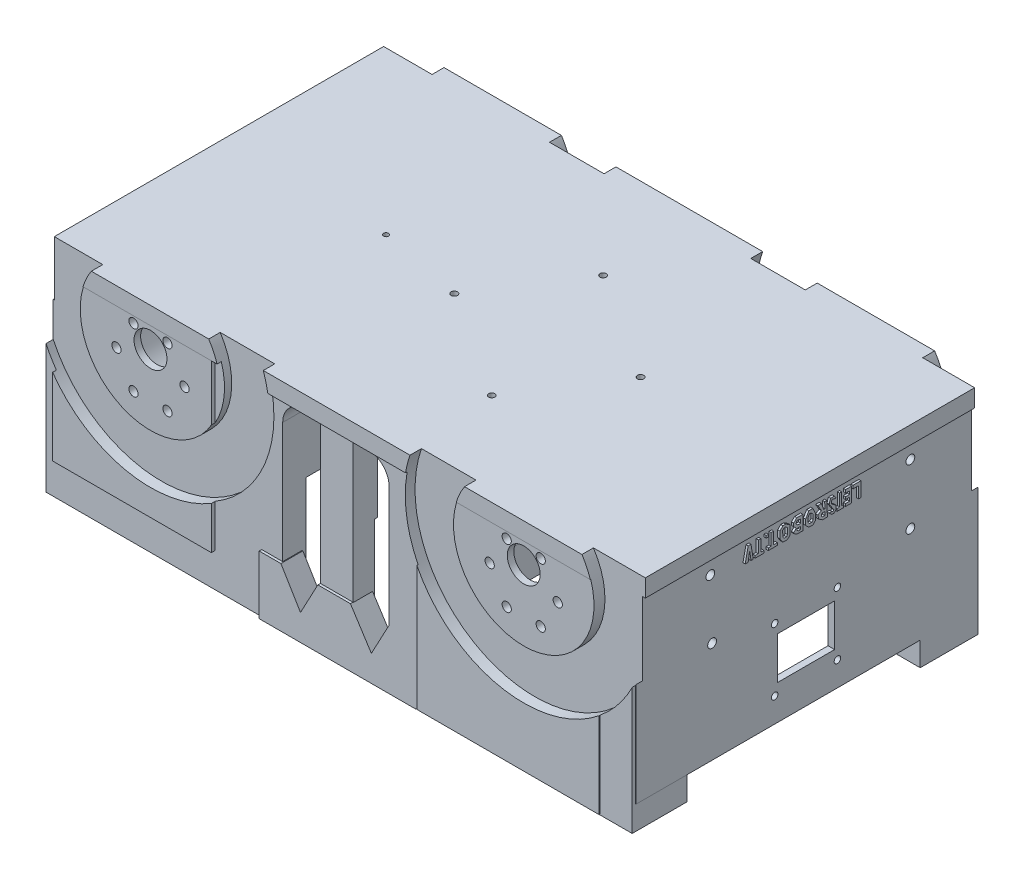
SolidWorks part; units mm, degrees
ref_plane "Front Plane" through (0, 0, 0) normal (0, 0, 1) x (1, 0, 0)
ref_plane "Top Plane" through (0, 0, 0) normal (0, 1, 0) x (1, 0, 0)
ref_plane "Right Plane" through (0, 0, 0) normal (1, 0, 0) x (0, 0, -1)
sketch "MotorHoldersSketch" plane through (0, 0, 0) normal (0, 0, 1) x (1, 0, 0)
  line L0 (0, 0) -> (170, 0) construction
  line L1 (0, 0) -> (0, 23.41) construction
  line L2 (170, 0) -> (170, 23.41) construction
  circle A0 centre (0, 0) radius 23.41
  circle A1 centre (170, 0) radius 23.41
ref_axis "MotorCenterAxis1" through (0, 0, 0) along (0, 0, 1)
ref_axis "MotorCenterAxis2" through (170, 0, 0) along (0, 0, 1)
extrude "MotorHolders" add sketch "MotorHoldersSketch" along normal blind 80 and the other way blind 80
sketch "Sketch3" plane through (0, 0, 0) normal (0, 0, 1) x (1, 0, 0)
  line L1 (1.9406, 21.133) -> (168.3435, 21.133)
  line L2 (1.9406, 21.133) -> (1.9406, 18.3155)
  line L3 (1.9406, 18.3155) -> (168.3435, 18.3155)
  line L4 (168.3435, 21.133) -> (168.3435, 18.3155)
sketch "Sketch4" plane through (0, 0, 0) normal (0, 1, 0) x (1, 0, 0)
  line L1 (221.2811, -76.3794) -> (-41.4939, -76.3794)
  line L2 (221.2811, -76.3794) -> (221.2811, 76.7331)
  line L3 (221.2811, 76.7331) -> (-41.4939, 76.7331)
  line L4 (-41.4939, -76.3794) -> (-41.4939, 76.7331)
extrude "Cut-Extrude1" cut sketch "Sketch4" against normal blind 26
ref_axis "Axis3" through (170, 0, 0) along (0, -1, 0)
sketch3d "ReferencePlanePosition"
  line L0 (170, 0, 0) -> (170, -34.8293, 0)
  line L1 (170, 0, 0) -> (170, -38.994, 0) construction
ref_plane "ReferencePlane" through (170, -34.8293, 0) normal (0, -1, 0) x (-1, 0, 0)
sketch "Sketch6" plane through (170, -34.8293, 0) normal (0, -1, 0) x (-1, 0, 0)
  line L1 (219.5858, 78.949) -> (112.1002, 78.949)
  line L2 (219.5858, 78.949) -> (219.5858, 65.5282)
  line L3 (219.5858, 65.5282) -> (112.1002, 65.5282)
  line L4 (112.1002, 78.949) -> (112.1002, 65.5282)
  line L5 (219.3147, -40.0209) -> (111.499, -40.0209)
  line L6 (219.3147, -40.0209) -> (219.3147, -78.2822)
  line L7 (219.3147, -78.2822) -> (111.499, -78.2822)
  line L8 (111.499, -40.0209) -> (111.499, -78.2822)
  line L9 (61.4891, 77.8627) -> (19.9904, 77.8627)
  line L10 (61.4891, 77.8627) -> (61.4891, 40.7512)
  line L11 (61.4891, 40.7512) -> (19.9904, 40.7512)
  line L12 (19.9904, 77.8627) -> (19.9904, 40.7512)
  line L13 (61.8484, -44.1716) -> (20.0852, -44.1716)
  line L14 (61.8484, -44.1716) -> (61.8484, -79.4437)
  line L15 (61.8484, -79.4437) -> (20.0852, -79.4437)
  line L16 (20.0852, -44.1716) -> (20.0852, -79.4437)
  line L17 (213.765, 73.0364) -> (192.9548, 73.0364)
  line L18 (213.765, 73.0364) -> (213.765, 71.0153)
  line L19 (213.765, 71.0153) -> (192.9548, 71.0153)
  line L20 (192.9548, 73.0364) -> (192.9548, 71.0153)
  line L21 (41.3552, 69.1777) -> (28.5109, 69.1777)
  line L22 (41.3552, 69.1777) -> (41.3552, 50.8413)
  line L23 (41.3552, 50.8413) -> (28.5109, 50.8413)
  line L24 (28.5109, 69.1777) -> (28.5109, 50.8413)
  line L25 (43.3068, -72.8101) -> (32.1723, -72.8101)
  line L26 (43.3068, -72.8101) -> (43.3068, -54.7747)
  line L27 (43.3068, -54.7747) -> (32.1723, -54.7747)
  line L28 (32.1723, -72.8101) -> (32.1723, -54.7747)
  line L29 (211.9411, -70.4881) -> (201.0982, -70.4881)
  line L30 (211.9411, -70.4881) -> (211.9411, -60.1404)
  line L31 (211.9411, -60.1404) -> (201.0982, -60.1404)
  line L32 (201.0982, -70.4881) -> (201.0982, -60.1404)
  line L33 (97.1795, 78.949) -> (79.4162, 78.949)
  line L34 (97.1795, 78.949) -> (97.1795, 67.7632)
  line L35 (97.1795, 67.7632) -> (79.4162, 67.7632)
  line L36 (79.4162, 78.949) -> (79.4162, 67.7632)
  line L37 (58.6711, 51.3198) -> (53.8697, 51.3198)
  line L38 (58.6711, 51.3198) -> (58.6711, 67.7632)
  line L39 (58.6711, 67.7632) -> (53.8697, 67.7632)
  line L40 (53.8697, 51.3198) -> (53.8697, 67.7632)
  line L41 (94.2281, -78.2822) -> (79.4162, -78.2822)
  line L42 (94.2281, -78.2822) -> (94.2281, -67.2515)
  line L43 (94.2281, -67.2515) -> (79.4162, -67.2515)
  line L44 (79.4162, -78.2822) -> (79.4162, -67.2515)
  line L45 (56.3648, -69.8638) -> (51.7107, -69.8638)
  line L46 (56.3648, -69.8638) -> (56.3648, -55.4273)
  line L47 (56.3648, -55.4273) -> (51.7107, -55.4273)
  line L48 (51.7107, -69.8638) -> (51.7107, -55.4273)
  line L49 (-20.7001, -79.4437) -> (-48.8506, -79.4437)
  line L50 (-20.7001, -79.4437) -> (-20.7001, -54.5097)
  line L51 (-20.7001, -54.5097) -> (-48.8506, -54.5097)
  line L52 (-48.8506, -79.4437) -> (-48.8506, -54.5097)
  line L53 (-18.3873, 77.8627) -> (-49.0581, 77.8627)
  line L54 (-18.3873, 77.8627) -> (-18.3873, 51.5325)
  line L55 (-18.3873, 51.5325) -> (-49.0581, 51.5325)
  line L56 (-49.0581, 77.8627) -> (-49.0581, 51.5325)
  line L57 (-41.8141, -72.8101) -> (-31.6362, -72.8101)
  line L58 (-41.8141, -72.8101) -> (-41.8141, -62.9794)
  line L59 (-41.8141, -62.9794) -> (-31.6362, -62.9794)
  line L60 (-31.6362, -72.8101) -> (-31.6362, -62.9794)
  line L61 (-31.6362, 69.1777) -> (-41.5347, 69.1777)
  line L62 (-31.6362, 69.1777) -> (-31.6362, 58.5421)
  line L63 (-31.6362, 58.5421) -> (-41.5347, 58.5421)
  line L64 (-41.5347, 69.1777) -> (-41.5347, 58.5421)
extrude "PowerBankHolders" add sketch "Sketch6" along normal blind 40 and the other way blind 59 separate body
sketch3d "3DSketch3"
  line L0 (170, 0, 0) -> (170, -64.5, 0) construction
ref_plane "Plane2" through (170, -64.5, 0) normal (0, -1, 0) x (-1, 0, 0)
sketch "Sketch7" plane through (170, -64.5, 0) normal (0, -1, 0) x (-1, 0, 0)
  line L1 (-9.5047, -80.801) -> (181.32, -80.801)
  line L2 (-9.5047, -80.801) -> (-9.5047, 73.8662)
  line L3 (-9.5047, 73.8662) -> (181.32, 73.8662)
  line L4 (181.32, -80.801) -> (181.32, 73.8662)
  line L5 (151.8712, -54.3972) -> (26.5361, -54.3972)
  line L6 (151.8712, -54.3972) -> (151.8712, 46.2413)
  line L7 (151.8712, 46.2413) -> (26.5361, 46.2413)
  line L8 (26.5361, -54.3972) -> (26.5361, 46.2413)
ref_point "Point1"
ref_point "Point2"
sketch3d "3DSketch11"
  line L0 (0, 0, -80) -> (170, 0, 80) construction
  point P4 (85, 0, 0)
sketch "MotorHolderExtrudeSketch" plane through (0, 0, 0) normal (0, 0, 1) x (1, 0, 0)
  circle A0 centre (170, 0) radius 20.415
  circle A1 centre (0, 0) radius 20.415
  circle A3 centre (0, 0) radius 23.41 construction
  circle A4 centre (170, 0) radius 23.41 construction
ref_point "TopOfMotors"
ref_plane "TangentToTopOfMotors" through (0, -20.415, 0) normal (0, 1, 0) x (1, 0, 0)
ref_axis "Axis4" through (85, 0, 0) along (0, -1, 0)
ref_plane "BottomOfPowerBankRegion" through (0, -20.425, 0) normal (0, 1, 0) x (1, 0, 0)
ref_point "CenterAtBottomOfPowerBank"
ref_plane "TopOfPowerBankPlane" through (0, -54.425, 0) normal (0, 1, 0) x (1, 0, 0)
sketch "Sketch13" plane through (0, -54.425, 0) normal (0, 1, 0) x (1, 0, 0)
  line L1 (-19.4498, 72.5454) -> (166.1636, 72.5454)
  line L2 (-19.4498, 72.5454) -> (-19.4498, -78.2051)
  line L3 (-19.4498, -78.2051) -> (166.1636, -78.2051)
  line L4 (166.1636, 72.5454) -> (166.1636, -78.2051)
  line L5 (19.3173, -49.583) -> (137.9607, -49.583)
  line L6 (19.3173, -49.583) -> (19.3173, -21.0549)
  line L7 (19.3173, -21.0549) -> (137.9607, -21.0549)
  line L8 (137.9607, -49.583) -> (137.9607, -21.0549)
  line L9 (19.3173, 56.6778) -> (137.9607, 56.6778)
  line L10 (19.3173, 56.6778) -> (19.3173, 36.3234)
  line L11 (19.3173, 36.3234) -> (137.9607, 36.3234)
  line L12 (137.9607, 56.6778) -> (137.9607, 36.3234)
  line L13 (19.3173, 18.3186) -> (137.9607, 18.3186)
  line L14 (19.3173, 18.3186) -> (19.3173, -7.3615)
  line L15 (19.3173, -7.3615) -> (137.9607, -7.3615)
  line L16 (137.9607, 18.3186) -> (137.9607, -7.3615)
sketch "Sketch15" plane through (150.0096, 0, 0) normal (1, 0, 0) x (0, 0, -1)
  line L1 (72.5313, -25.7765) -> (45.7099, -25.7765)
  line L2 (72.5313, -25.7765) -> (72.5313, -24.2242)
  line L3 (72.5313, -24.2242) -> (45.7099, -24.2242)
  line L4 (45.7099, -25.7765) -> (45.7099, -24.2242)
ref_plane "Plane6" through (0, 0, 0) normal (0, 0, 1) x (1, 0, 0)
sketch "MotorGeometry1" plane through (0, 0, 0) normal (0, 0, 1) x (1, 0, 0)
  line L0 (170, 0) -> (170, -13.42)
  line L1 (170, 0) -> (170, -34.8293) construction
  line L2 (170, -13.42) -> (162.25, -13.42) construction
  line L3 (170, -13.42) -> (177.75, -13.42) construction
  line L4 (170, -13.42) -> (170, 7) construction
  line L5 (170, 0) -> (185.5, 0) construction
  line L6 (170, 0) -> (154.5, 0) construction
  line L7 (170, 0) -> (170, 13.42) construction
  line L8 (170, 0) -> (170, 23.41) construction
  line L9 (170, 13.42) -> (177.75, 13.42) construction
  line L10 (170, 13.42) -> (162.25, 13.42)
ref_axis "BoltAxisA" through (185.5, 0, 0) along (0, 0, 1)
ref_axis "BoltAxisB" through (177.75, -13.42, 0) along (0, 0, 1)
ref_axis "BoltAxisC" through (162.25, -13.42, 0) along (0, 0, 1)
ref_axis "BoltAxisD" through (154.5, 0, 0) along (0, 0, 1)
ref_axis "BoltAxisE" through (162.25, 13.42, 0) along (0, 0, 1)
ref_axis "BoltAxisF" through (177.75, 13.42, 0) along (0, 0, 1)
ref_point "Point6"
ref_point "Point7"
ref_point "Point8"
ref_point "Point9"
ref_point "Point10"
ref_point "Point11"
ref_point "Point12"
ref_point "Point13"
ref_point "Point14"
ref_point "Point15"
ref_point "Point16"
ref_point "Point17"
ref_plane "Plane7" through (0, 0, 0) normal (0, 0, 1) x (1, 0, 0)
sketch "MotorGeometry2" plane through (0, 0, 0) normal (0, 0, 1) x (1, 0, 0)
  line L0 (0, 0) -> (0, -13.42) construction
  line L1 (0, -13.42) -> (7.75, -13.42) construction
  line L2 (0, -13.42) -> (-7.75, -13.42) construction
  line L3 (0, 0) -> (0, 13.42)
  line L4 (0, -13.42) -> (0, 7) construction
  line L5 (0, 13.42) -> (7.75, 13.42) construction
  line L6 (0, 13.42) -> (-7.75, 13.42) construction
  line L7 (0, 0) -> (15.5, 0) construction
  line L8 (0, 0) -> (-15.5, 0) construction
  line L9 (0, 0) -> (0, 23.41) construction
ref_axis "Axis11" through (15.5, 0, 0) along (0, 0, 1)
ref_axis "Axis12" through (7.75, 13.42, 0) along (0, 0, 1)
ref_axis "Axis13" through (-7.75, 13.42, 0) along (0, 0, 1)
ref_axis "Axis14" through (-15.5, 0, 0) along (0, 0, 1)
ref_axis "Axis15" through (-7.75, -13.42, 0) along (0, 0, 1)
ref_axis "Axis16" through (7.75, -13.42, 0) along (0, 0, 1)
ref_point "Point18"
ref_point "Point19"
ref_point "Point20"
ref_point "Point21"
ref_point "Point22"
ref_point "Point23"
ref_point "Point24"
ref_point "Point25"
ref_point "Point26"
ref_point "Point27"
ref_point "Point28"
ref_point "Point29"
ref_plane "BottomPlane" through (0, 19.575, 0) normal (0, 1, 0) x (1, 0, 0)
ref_axis "OutputShaftReference1" through (0, 7, 0) along (0, 0, 1)
ref_point "Point35"
ref_axis "OutputShaftReference2" through (170, 7, 0) along (0, 0, 1)
sketch "Sketch21" plane through (0, 19.575, 0) normal (0, 1, 0) x (1, 0, 0)
  line L0 (219.6842, -79.5488) -> (-50.341, -79.5488) construction
  line L1 (-50.341, -79.5488) -> (-50.341, 79.7899) construction
  line L2 (-50.341, 79.7899) -> (219.6842, 79.7899) construction
  line L3 (219.6842, 79.7899) -> (219.6842, -79.5488) construction
  circle A0 centre (85, 0) radius 156.3953
extrude "BottomPlate" add sketch "Sketch21" along normal blind 5 and the other way blind 3
ref_plane "HoleReferencePlane1" through (0, 0, 80) normal (0, 0, 1) x (1, 0, 0)
ref_point "OutputShaftPosition3"
ref_point "OutputShaftPosition1"
sketch "Sketch23" plane through (0, 0, 80) normal (0, 0, 1) x (1, 0, 0)
  line L1 (27.7411, -59.3229) -> (-44.5901, -59.3229)
  line L2 (27.7411, -59.3229) -> (27.7411, 21.8402)
  line L3 (27.7411, 21.8402) -> (-44.5901, 21.8402)
  line L4 (-44.5901, -59.3229) -> (-44.5901, 21.8402)
  line L5 (121.3218, 21.8402) -> (204.258, 21.8402)
  line L6 (121.3218, 21.8402) -> (121.3218, -74.371)
  line L7 (121.3218, -74.371) -> (204.258, -74.371)
  line L8 (204.258, 21.8402) -> (204.258, -74.371)
extrude "MotorMountingSupport1" add sketch "Sketch23" against normal blind 6
ref_plane "HoleReferencePlane2" through (0, 0, -80) normal (0, 0, -1) x (-1, 0, 0)
ref_point "OutputShaftPosition4"
ref_point "OutputShaftPosition2"
sketch "Sketch24" plane through (0, 0, -80) normal (0, 0, -1) x (-1, 0, 0)
  line L1 (-202.1905, -75.2023) -> (-123.8485, -75.2023)
  line L2 (-202.1905, -75.2023) -> (-202.1905, 19.2374)
  line L3 (-202.1905, 19.2374) -> (-123.8485, 19.2374)
  line L4 (-123.8485, -75.2023) -> (-123.8485, 19.2374)
  line L5 (-24.3642, -64.1521) -> (29.5505, -64.1521)
  line L6 (-24.3642, -64.1521) -> (-24.3642, 22.5226)
  line L7 (-24.3642, 22.5226) -> (29.5505, 22.5226)
  line L8 (29.5505, -64.1521) -> (29.5505, 22.5226)
extrude "MotorMountingSuppor2" add sketch "Sketch24" against normal blind 6
sketch "Sketch17" plane through (0, 0, 80) normal (0, 0, 1) x (1, 0, 0)
  circle A0 centre (185.5, 0) radius 2.1
  circle A1 centre (177.75, -13.42) radius 2.1
  circle A2 centre (162.25, -13.42) radius 2.1
  circle A3 centre (154.5, 0) radius 2.1
  circle A4 centre (162.25, 13.42) radius 2.1
  circle A5 centre (177.75, 13.42) radius 2.1
  circle A6 centre (170, 7) radius 7.5
extrude "MotorHoles1" cut sketch "Sketch17" against normal blind 31.5
sketch "Sketch19" plane through (0, 0, -80) normal (0, 0, -1) x (-1, 0, 0)
  circle A0 centre (-185.5, 0) radius 2.1
  circle A1 centre (-177.75, -13.42) radius 2.1
  circle A2 centre (-162.25, -13.42) radius 2.1
  circle A3 centre (-154.5, 0) radius 2.1
  circle A4 centre (-162.25, 13.42) radius 2.1
  circle A5 centre (-177.75, 13.42) radius 2.1
  circle A6 centre (-170, 7) radius 7.5
sketch "BoltHolesSketch3" plane through (0, 0, 80) normal (0, 0, 1) x (1, 0, 0)
  circle A0 centre (7.75, -13.42) radius 2.1
  circle A1 centre (15.5, 0) radius 2.1
  circle A2 centre (7.75, 13.42) radius 2.1
  circle A3 centre (-7.75, 13.42) radius 2.1
  circle A4 centre (-15.5, 0) radius 2.1
  circle A5 centre (-7.75, -13.42) radius 2.1
  circle A6 centre (0, 7) radius 7.5
extrude "Cut-Extrude4" cut sketch "Sketch19" against normal blind 30
extrude "MotorHoles3" cut sketch "BoltHolesSketch3" against normal blind 31.5
sketch "BoltHolesSketch4" plane through (0, 0, -80) normal (0, 0, -1) x (-1, 0, 0)
  circle A0 centre (-15.5, 0) radius 2.1
  circle A1 centre (-7.75, 13.42) radius 2.1
  circle A2 centre (7.75, 13.42) radius 2.1
  circle A3 centre (15.5, 0) radius 2.1
  circle A4 centre (7.75, -13.42) radius 2.1
  circle A5 centre (-7.75, -13.42) radius 2.1
  circle A6 centre (0, 7) radius 7.5
extrude "MotorHoles4" cut sketch "BoltHolesSketch4" against normal blind 15
ref_plane "Front" through (219.0581, 0, 0) normal (1, 0, 0) x (0, 0, -1)
sketch "Sketch29" plane through (219.0581, 0, 0) normal (1, 0, 0) x (0, 0, -1)
  line L1 (76.6955, -63.9254) -> (-77.9397, -63.9254)
  line L2 (76.6955, -63.9254) -> (76.6955, 20.2062)
  line L3 (76.6955, 20.2062) -> (-77.9397, 20.2062)
  line L4 (-77.9397, -63.9254) -> (-77.9397, 20.2062)
  line L5 (-13.4507, -48.1531) -> (12.5493, -48.1531)
  line L6 (-13.4507, -48.1531) -> (-13.4507, -28.9404)
  line L7 (-13.4507, -28.9404) -> (12.5493, -28.9404)
  line L8 (12.5493, -48.1531) -> (12.5493, -28.9404)
extrude "Boss-Extrude8" add sketch "Sketch29" against normal blind 3
ref_plane "RaspberryPiBasePlane" through (0, 16.575, 0) normal (0, -1, 0) x (-1, 0, 0)
sketch "Sketch27" plane through (0, 16.575, 0) normal (0, -1, 0) x (-1, 0, 0)
  line L1 (31.6337, 64.5517) -> (-194.8264, 64.5517)
  line L2 (31.6337, 64.5517) -> (31.6337, -65.4335)
  line L3 (31.6337, -65.4335) -> (-194.8264, -65.4335)
  line L4 (-194.8264, 64.5517) -> (-194.8264, -65.4335)
extrude "Boss-Extrude6" add sketch "Sketch27" against normal blind 3
ref_plane "Plane12" through (0, -74.8293, 0) normal (0, -1, 0) x (-1, 0, 0)
sketch "Sketch28" plane through (0, -74.8293, 0) normal (0, -1, 0) x (-1, 0, 0)
  line L1 (-189.3897, -97.3973) -> (-123.0026, -97.3973)
  line L2 (-189.3897, -97.3973) -> (-189.3897, 96.7192)
  line L3 (-189.3897, 96.7192) -> (-123.0026, 96.7192)
  line L4 (-123.0026, -97.3973) -> (-123.0026, 96.7192)
sketch "Sketch40" plane through (0, 16.575, 0) normal (0, -1, 0) x (1, 0, 0)
  line L1 (-49.5858, -65.5282) -> (-15.7443, -65.5282)
  line L2 (-49.5858, -65.5282) -> (-49.5858, -33.9964)
  line L3 (-49.5858, -33.9964) -> (-15.7443, -33.9964)
  line L4 (-15.7443, -65.5282) -> (-15.7443, -33.9964)
extrude "Boss-Extrude11" add sketch "Sketch40" along normal blind 40
fillet "Fillet2" radius 15 1 edges at (-33.0588, 16.575, -33.9964) type face fillet first side face at (-28.7089, -2.1691, -33.9964) second side face at (85, 16.575, 156.3953)
fillet "Fillet3" radius 15 1 edges at (-32.6651, -23.425, -65.5282) type face fillet first side face at (-5.65, -13.42, -65.5282) second side face at (-32.6651, -23.425, -49.7623)
sketch "Sketch11" plane through (0, -20.425, 0) normal (0, 1, 0) x (1, 0, 0)
  line L0 (-34.2162, 4.2922) -> (204.2162, -4.2922) construction
  line L5 (-34.2162, -64.7581) -> (-34.2162, 73.3425)
  line L6 (204.2162, 63.611) -> (204.2162, -72.1954)
  line L7 (204.2162, -72.1954) -> (-34.2162, -64.7581)
  line L8 (204.2162, 63.611) -> (-34.2162, 73.3425)
  circle A0 centre (85, 0) radius 104 construction
extrude "PowerBankCut" cut sketch "Sketch11" against normal up to surface (54.4043 mm away) up to face at (204.7754, -74.8293, 66.9767)
extrude "MotorHolderCut" cut sketch "MotorHolderExtrudeSketch" against normal blind 77 and the other way blind 77
sketch "Sketch31" plane through (219.0581, 0, 0) normal (1, 0, 0) x (0, 0, -1)
  line L0 (-11.9853, 13.4398) -> (-13.3624, 12.0627)
  line L1 (-13.3624, 12.0627) -> (-13.3624, 8.9452)
  line L2 (-11.9853, 6.9748) -> (-13.3624, 8.9452)
  line L3 (23.5583, 6.7877) -> (23.5583, 13.4398)
  line L4 (23.5583, 13.4398) -> (19.9736, 13.4398)
  line L5 (19.9736, 13.4398) -> (19.9736, 12.0236)
  line L6 (19.9736, 12.0236) -> (22.4953, 12.0236)
  line L7 (22.4953, 12.0236) -> (22.4953, 6.7877)
  line L8 (23.5583, 6.7877) -> (22.4953, 6.7877)
  line L9 (19.3464, 13.4398) -> (19.3464, 6.7877)
  line L10 (19.3464, 6.7877) -> (16.5174, 6.7877)
  line L11 (16.5174, 6.7877) -> (16.5174, 7.9482)
  line L12 (16.5174, 7.9482) -> (18.3741, 7.9482)
  line L13 (18.3741, 7.9482) -> (18.3741, 9.5315)
  line L14 (18.3741, 9.5315) -> (16.5174, 9.5315)
  line L15 (16.5174, 9.5315) -> (16.5174, 10.6274)
  line L16 (16.5174, 10.6274) -> (18.3741, 10.6274)
  line L17 (18.3741, 10.6274) -> (18.3741, 12.0236)
  line L18 (18.3741, 12.0236) -> (16.5174, 12.0236)
  line L19 (16.5174, 12.0236) -> (16.5174, 13.4398)
  line L20 (19.3464, 13.4398) -> (16.5174, 13.4398)
  line L21 (15.6231, 6.7877) -> (15.6231, 7.9482)
  line L22 (15.6231, 6.7877) -> (12.7162, 6.7877)
  line L23 (12.7162, 6.7877) -> (12.7162, 7.9482)
  line L24 (12.7162, 7.9482) -> (13.819, 7.9482)
  line L25 (13.819, 7.9482) -> (13.819, 13.4398)
  line L26 (13.819, 13.4398) -> (14.771, 13.4398)
  line L27 (14.771, 13.4398) -> (14.771, 7.9482)
  line L28 (15.6231, 7.9482) -> (14.771, 7.9482)
  line L29 (9.0737, 7.9482) -> (10.2342, 6.7877)
  line L30 (10.2342, 6.7877) -> (11.2446, 6.7877)
  line L31 (11.2446, 6.7877) -> (12.156, 7.699)
  line L32 (12.156, 7.699) -> (12.156, 9.5315)
  line L33 (12.156, 9.5315) -> (10.2342, 10.8736)
  line L34 (9.0737, 7.9482) -> (10.2342, 7.9482)
  line L35 (10.2342, 7.9482) -> (10.6704, 7.699)
  line L36 (10.6704, 7.699) -> (11.2446, 8.0737)
  line L37 (11.2446, 8.0737) -> (9.0737, 11.4008)
  line L38 (9.0737, 11.4008) -> (9.6875, 13.4398)
  line L39 (9.6875, 13.4398) -> (11.4814, 13.4398)
  line L40 (11.4814, 13.4398) -> (12.156, 12.3409)
  line L41 (12.156, 12.3409) -> (11.2446, 12.3409)
  line L42 (11.2446, 12.3409) -> (10.6704, 12.772)
  line L43 (10.6704, 12.772) -> (10.1086, 12.0236)
  line L44 (10.1086, 12.0236) -> (10.2342, 10.8736)
  line L45 (-20.664, 6.9748) -> (-20.664, 8.0737)
  line L46 (-18.6605, 13.4398) -> (-19.6346, 13.4398)
  line L47 (-18.6605, 13.4398) -> (-18.6605, 12.3409)
  line L48 (-18.6605, 12.3409) -> (-19.6346, 12.3409)
  line L49 (-19.6346, 13.4398) -> (-19.6346, 12.3409)
  line L50 (-20.664, 8.0737) -> (-22.0801, 8.0737)
  line L51 (-20.664, 6.9748) -> (-24.6188, 6.9748)
  line L52 (-24.6188, 6.9748) -> (-24.6188, 8.0737)
  line L53 (-24.6188, 8.0737) -> (-23.2262, 8.0737)
  line L54 (-22.0801, 8.0737) -> (-22.0801, 13.4398)
  line L55 (-22.0801, 13.4398) -> (-23.2262, 13.4398)
  line L56 (8.0122, 13.4398) -> (8.253, 6.7877)
  line L57 (8.253, 6.7877) -> (6.0128, 6.7877)
  line L58 (6.0128, 6.7877) -> (4.2685, 7.9482)
  line L59 (4.2685, 7.9482) -> (3.8991, 9.7863)
  line L60 (3.8991, 9.7863) -> (5.5426, 10.6274)
  line L61 (5.5426, 10.6274) -> (3.8991, 13.4398)
  line L62 (3.8991, 13.4398) -> (5.5426, 13.4398)
  line L63 (5.5426, 13.4398) -> (6.5701, 10.6274)
  line L64 (6.5701, 10.6274) -> (7.1329, 10.6274)
  line L65 (7.1329, 10.6274) -> (7.0311, 13.4398)
  line L66 (7.0311, 13.4398) -> (8.0122, 13.4398)
  line L67 (1.6684, 13.4398) -> (-0.1827, 13.4398)
  line L68 (-0.1827, 13.4398) -> (-1.6538, 10.8736)
  line L69 (-1.6538, 10.8736) -> (-1.6538, 8.4246)
  line L70 (-1.6538, 8.4246) -> (-0.1827, 6.9535)
  line L71 (-0.1827, 6.9535) -> (1.6684, 6.9535)
  line L72 (1.6684, 6.9535) -> (2.9495, 8.2346)
  line L73 (2.9495, 8.2346) -> (2.9495, 10.6274)
  line L74 (2.9495, 10.6274) -> (1.6684, 13.4398)
  line L75 (-2.9468, 6.9535) -> (-2.9468, 13.4398)
  line L76 (-2.9468, 13.4398) -> (-5.696, 13.4398)
  line L77 (-5.696, 13.4398) -> (-7.1123, 12.0236)
  line L78 (-7.1123, 12.0236) -> (-7.1123, 10.6274)
  line L79 (-7.1123, 10.6274) -> (-5.9341, 9.4492)
  line L80 (-5.9341, 9.4492) -> (-7.1123, 8.2711)
  line L81 (-7.1123, 8.2711) -> (-7.1123, 7.9482)
  line L82 (-7.1123, 7.9482) -> (-5.696, 6.9535)
  line L83 (-5.696, 6.9535) -> (-2.9468, 6.9535)
  line L84 (-9.9534, 6.9535) -> (-8.8331, 8.0737)
  line L85 (-8.8331, 8.0737) -> (-8.8331, 12.3409)
  line L86 (-8.8331, 12.3409) -> (-10.7011, 13.4398)
  line L87 (-10.7011, 13.4398) -> (-11.9853, 13.4398)
  line L88 (-23.2262, 13.4398) -> (-23.2262, 8.0737)
  line L89 (-25.5187, 6.9748) -> (-26.5366, 13.4398)
  line L90 (-26.5366, 13.4398) -> (-27.8126, 13.4398)
  line L91 (-11.9853, 6.9748) -> (-9.9534, 6.9535)
  line L92 (-14.5404, 6.9748) -> (-18.6605, 6.9748)
  line L93 (-18.6605, 6.9748) -> (-18.6605, 8.0737)
  line L94 (-18.6605, 8.0737) -> (-17.3325, 8.0737)
  line L95 (-17.3325, 8.0737) -> (-17.3325, 13.4398)
  line L96 (-17.3325, 13.4398) -> (-16.1754, 13.4398)
  line L97 (-16.1754, 13.4398) -> (-16.1754, 8.0737)
  line L98 (-16.1754, 8.0737) -> (-14.5404, 8.0737)
  line L99 (-14.5404, 8.0737) -> (-14.5404, 6.9748)
  line L100 (1.1066, 8.2346) -> (1.8172, 8.9452)
  line L101 (1.8172, 8.9452) -> (1.8172, 11.1371)
  line L102 (1.8172, 11.1371) -> (0.8255, 12.1288)
  line L103 (0.8255, 12.1288) -> (0.2118, 12.1288)
  line L104 (0.2118, 12.1288) -> (-0.525, 11.1371)
  line L105 (-0.525, 11.1371) -> (-0.6294, 9.2253)
  line L106 (-0.6294, 9.2253) -> (0.0159, 8.2739)
  line L107 (0.0159, 8.2739) -> (1.1066, 8.2346)
  line L108 (-4.0608, 9.2253) -> (-5.4172, 9.2253)
  line L109 (-5.4172, 9.2253) -> (-5.696, 8.4246)
  line L110 (-5.696, 8.4246) -> (-4.9992, 7.9482)
  line L111 (-4.9992, 7.9482) -> (-4.0608, 7.9482)
  line L112 (-4.0608, 7.9482) -> (-4.0608, 9.2253)
  line L113 (-3.8961, 10.3794) -> (-3.8961, 12.1288)
  line L114 (-3.8961, 12.1288) -> (-5.5739, 12.3409)
  line L115 (-5.5739, 12.3409) -> (-6.0661, 11.2541)
  line L116 (-6.0661, 11.2541) -> (-5.257, 10.3794)
  line L117 (-5.257, 10.3794) -> (-3.8961, 10.3794)
  line L118 (-10.3458, 8.2739) -> (-9.9534, 8.9452)
  line L119 (-9.9534, 8.9452) -> (-9.9534, 11.8216)
  line L120 (-9.9534, 11.8216) -> (-10.9018, 12.3409)
  line L121 (-10.9018, 12.3409) -> (-11.4919, 12.3409)
  line L122 (-11.4919, 12.3409) -> (-12.1481, 11.6848)
  line L123 (-12.1481, 11.6848) -> (-11.9853, 8.9452)
  line L124 (-11.9853, 8.9452) -> (-11.4919, 8.2739)
  line L125 (-11.4919, 8.2739) -> (-10.3458, 8.2739)
  line L126 (7.1329, 7.9482) -> (7.1329, 9.5315)
  line L127 (7.1329, 9.5315) -> (6.0128, 9.5315)
  line L128 (6.0128, 9.5315) -> (5.5426, 9.0613)
  line L129 (5.5426, 9.0613) -> (5.5426, 8.4246)
  line L130 (5.5426, 8.4246) -> (6.0932, 7.874)
  line L131 (6.0932, 7.874) -> (7.1329, 7.9482)
  line L132 (-27.8126, 13.4398) -> (-29.1855, 6.9748)
  line L133 (-29.1855, 6.9748) -> (-27.8126, 6.9748)
  line L134 (-27.8126, 6.9748) -> (-27.1746, 11.2541)
  line L135 (-27.1746, 11.2541) -> (-26.5008, 6.9748)
  line L136 (-26.5008, 6.9748) -> (-25.5187, 6.9748)
extrude "Label" add sketch "Sketch31" along normal blind 1
sketch "Sketch32" plane through (0, 19.575, 0) normal (0, 1, 0) x (1, 0, 0)
  line L1 (-48.8137, 80.4301) -> (220.392, 80.4301)
  line L2 (-48.8137, 80.4301) -> (-48.8137, -80.215)
  line L3 (-48.8137, -80.215) -> (220.392, -80.215)
  line L4 (220.392, 80.4301) -> (220.392, -80.215)
  line L5 (283.5566, -218.7268) -> (-136.4889, -218.7268)
  line L8 (-136.4889, -218.7268) -> (-136.4889, 206.3198)
  line L10 (283.5566, 206.3198) -> (283.5566, -218.7268)
  line L13 (283.5566, 206.3198) -> (-136.4889, 206.3198)
extrude "BaseDefiningCut" cut sketch "Sketch32" along normal blind 20 and the other way blind 20
sketch "Sketch39" plane through (0, 16.575, 0) normal (0, -1, 0) x (1, 0, 0)
  line L1 (-48.8137, -65.5282) -> (-16.0867, -65.5282)
  line L2 (-48.8137, -65.5282) -> (-48.8137, -46.28)
  line L3 (-48.8137, -46.28) -> (-16.0867, -46.28)
  line L4 (-16.0867, -65.5282) -> (-16.0867, -46.28)
sketch "Sketch35" plane through (0, 0, -80.4301) normal (0, 0, -1) x (-1, 0, 0)
  line L0 (69.0502, 16.3777) -> (-36.4474, 27.6206)
  line L1 (-36.4474, 27.6206) -> (71.6404, 26.1593)
  line L2 (69.0502, 16.3777) -> (71.6404, 26.1593)
  line L3 (-223.8844, 30.8145) -> (-223.8844, 17.5678)
  line L4 (-223.8844, 17.5678) -> (-116.0163, 30.8145)
  line L5 (-116.0163, 30.8145) -> (-223.8844, 30.8145)
sketch "Sketch36" plane through (-49.3147, 0, 0) normal (-1, 0, 0) x (0, 0, 1)
  line L0 (40.0209, -74.8293) -> (40.0209, -38.3689) construction
  line L1 (55.0666, -55.0742) -> (78.2822, -55.0742) construction
  line L2 (40.0209, -38.3689) -> (40.0209, -74.8293) construction
  line L3 (78.2822, -0.425) -> (78.2822, -74.8293) construction
  circle A1 centre (55.0666, -55.0742) radius 14
extrude "HoleForPowerConnector" cut sketch "Sketch36" against normal blind 17
sketch "Sketch37" plane through (0, -20.425, 0) normal (0, -1, 0) x (1, 0, 0)
  line L1 (144.416, -35.6729) -> (89.0759, -35.6729)
  line L2 (144.416, -35.6729) -> (144.416, -65.4438)
  line L3 (144.416, -65.4438) -> (89.0759, -65.4438)
  line L4 (89.0759, -35.6729) -> (89.0759, -65.4438)
extrude "Cut-Extrude7" cut sketch "Sketch37" against normal blind 36
sketch "Sketch38" plane through (0, 16.575, 0) normal (0, -1, 0) x (1, 0, 0)
  line L0 (25.9964, 80.215) -> (25.9964, -1.3165) construction
  line L1 (-48.8137, 80.215) -> (219.2574, 80.215) construction
  circle A0 centre (25.9964, -1.3165) radius 1.1452
extrude "Cut-Extrude8" cut sketch "Sketch38" against normal blind 10
sketch "Sketch41" plane through (0, 0, 80) normal (0, 0, 1) x (1, 0, 0)
  circle A0 centre (0, 7) radius 32
  circle A1 centre (0, 7) radius 54.5
extrude "SpaceForWheel1" cut sketch "Sketch41" against normal blind 5 and the other way blind 10
sketch "Sketch42" plane through (0, 0, 80) normal (0, 0, 1) x (1, 0, 0)
  circle A0 centre (170, 7) radius 32
  circle A1 centre (170, 7) radius 54.5
extrude "Cut-Extrude10" cut sketch "Sketch42" against normal blind 5 and the other way blind 10
sketch "Sketch43" plane through (0, 0, -80) normal (0, 0, -1) x (-1, 0, 0)
  circle A0 centre (-170, 7) radius 32
  circle A1 centre (-170, 7) radius 54.5
extrude "Cut-Extrude11" cut sketch "Sketch43" against normal blind 5 and the other way blind 10
sketch "Sketch44" plane through (0, 0, -80) normal (0, 0, -1) x (-1, 0, 0)
  circle A0 centre (0, 7) radius 32
  circle A1 centre (0, 7) radius 54.5
extrude "Cut-Extrude12" cut sketch "Sketch44" against normal blind 5 and the other way blind 10
sketch "Sketch45" plane through (-48.8137, 0, 0) normal (-1, 0, 0) x (0, 0, 1)
  line L0 (-75, 24.575) -> (75, 24.575) construction
  line L1 (-72.1063, 24.575) -> (42.0312, 24.575)
  line L2 (-72.1063, 24.575) -> (-72.1063, -74.1222)
  line L3 (-72.1063, -74.1222) -> (42.0312, -74.1222)
  line L4 (42.0312, 24.575) -> (42.0312, -74.1222)
extrude "BackPlate" add sketch "Sketch45" against normal blind 2
sketch "Sketch46" plane through (0, -74.8293, 0) normal (0, -1, 0) x (1, 0, 0)
  line L1 (97.1427, -74.9256) -> (213.5256, -74.9256)
  line L2 (97.1427, -74.9256) -> (97.1427, -71.5234)
  line L3 (97.1427, -71.5234) -> (213.5256, -71.5234)
  line L4 (213.5256, -74.9256) -> (213.5256, -71.5234)
  line L5 (97.1427, 72.8226) -> (213.5256, 72.8226)
  line L6 (97.1427, 72.8226) -> (97.1427, 77.4687)
  line L7 (97.1427, 77.4687) -> (213.5256, 77.4687)
  line L8 (213.5256, 72.8226) -> (213.5256, 77.4687)
fillet "Fillet8" radius 10 1 edges at (57.8998, 16.575, -72.2386) type face fillet first side face at (57.8998, -26.2264, -71.3533) second side face at (25.9964, 16.575, -2.4617)
fillet "Fillet9" radius 10 1 edges at (108.5109, 16.575, -59.3069) type face fillet first side face at (108.5109, -15.7761, -62.8937) second side face at (25.9964, 16.575, -2.4617)
fillet "Fillet10" radius 10 1 edges at (108.1516, 16.575, 61.8076) type face fillet first side face at (108.1516, -26.2264, 64.2714) second side face at (25.9964, 16.575, -2.4617)
sketch "Sketch49" plane through (0, 0, 80) normal (0, 0, 1) x (1, 0, 0)
  line L0 (27.7411, -8.9509) -> (27.7411, 16.575) construction
  circle A0 centre (27.7411, 12.953) radius 3.5831
fillet "Fillet11" radius 10 1 edges at (58.501, 16.575, 59.1515) type face fillet first side face at (58.501, -26.2264, 61.9844) second side face at (25.9964, 16.575, -2.4617)
sketch "Sketch50" plane through (0, -74.8293, 0) normal (0, -1, 0) x (1, 0, 0)
  line L1 (-49.3147, 40.0209) -> (-40.7689, 40.0209)
  line L2 (-49.3147, 40.0209) -> (-49.3147, 52.7795)
  line L3 (-49.3147, 52.7795) -> (-40.7689, 52.7795)
  line L4 (-40.7689, 40.0209) -> (-40.7689, 52.7795)
  line L5 (-49.5858, -65.5282) -> (-35.8777, -65.5282)
  line L6 (-49.5858, -65.5282) -> (-49.5858, -77.7316)
  line L7 (-49.5858, -77.7316) -> (-35.8777, -77.7316)
  line L8 (-35.8777, -65.5282) -> (-35.8777, -77.7316)
sketch "Sketch51" plane through (0, 0, 79.4437) normal (0, 0, 1) x (1, 0, 0)
  line L0 (108.1516, -47.9804) -> (100.047, -63.1792)
  line L1 (108.1516, 6.575) -> (108.1516, -74.8293) construction
  line L2 (100.047, -63.1792) -> (90.5163, -48.3368)
  line L3 (90.5163, -48.3368) -> (75.6762, -48.3368)
  line L4 (75.6762, -48.3368) -> (67.7615, -63.1792)
  line L5 (67.7615, -63.1792) -> (58.8398, -48.3368)
  line L6 (58.8398, -48.3368) -> (48.9291, -48.3368)
  line L7 (48.9291, -48.3368) -> (48.9291, -75.0407)
  line L8 (48.9291, -75.0407) -> (120.2514, -75.0407)
  line L9 (120.2514, -75.0407) -> (120.2514, -47.9804)
  line L10 (120.2514, -47.9804) -> (108.1516, -47.9804)
extrude "Boss-Extrude12" add sketch "Sketch51" against normal blind 10
sketch "Sketch53" plane through (0, 0, -77.8627) normal (0, 0, -1) x (-1, 0, 0)
  line L1 (-57.7992, -55.7616) -> (-64.6668, -65.1072)
  line L2 (-64.6668, -65.1072) -> (-72.7541, -55.7616)
  line L3 (-72.7541, -55.7616) -> (-90.6554, -55.7616)
  line L4 (-90.6554, -55.7616) -> (-98.6681, -65.1072)
  line L5 (-98.6681, -65.1072) -> (-108.5109, -55.7616)
  line L6 (-108.5109, 6.575) -> (-108.5109, -74.8293) construction
  line L7 (-108.5109, -55.7616) -> (-123.8485, -55.7616)
  line L8 (-123.8485, -21.9878) -> (-123.8485, -74.8293) construction
  line L9 (-123.8485, -55.7616) -> (-123.8485, -74.8293)
  line L10 (-123.8485, -74.8293) -> (-52.4383, -74.8293)
  line L11 (-52.4383, -74.8293) -> (-52.4383, -55.7616)
  line L12 (-52.4383, -55.7616) -> (-57.7992, -55.7616)
extrude "Boss-Extrude13" add sketch "Sketch53" against normal blind 9
sketch "HolesForRasPiMounting" plane through (0, 16.575, 0) normal (0, -1, 0) x (1, 0, 0)
  circle A0 centre (91.4678, -34.696) radius 1.4146
  circle A1 centre (64.7805, 6.3989) radius 1.4536
  circle A2 centre (140.1107, -3.1069) radius 1.4303
  circle A3 centre (113.4234, 37.9879) radius 1.4064
extrude "Cut-Extrude13" cut sketch "HolesForRasPiMounting" against normal through all
sketch "HolesForChargingPlatesSketch" plane through (219.0581, 0, 0) normal (1, 0, 0) x (0, 0, -1)
  circle A0 centre (47.06, -17.739) radius 2
  circle A1 centre (-43.2542, -17.739) radius 2
  circle A2 centre (-44.0465, 9.5376) radius 2
  circle A3 centre (47.06, 9.5376) radius 2
extrude "HolesForChargingPlates" cut sketch "HolesForChargingPlatesSketch" against normal up to surface (3 mm away) up to face at (216.0581, -23.6752, 1.4886)
sketch "Sketch55" plane through (219.0581, 0, 0) normal (1, 0, 0) x (0, 0, -1)
  line L0 (-13.4507, -48.1531) -> (12.5493, -28.9404) construction
  line L1 (12.5493, -48.1531) -> (-13.4507, -28.9404) construction
ref_point "CamerCutCenter"
ref_axis "CameraCutAxis" through (219.0581, -38.5467, 0.4507) along (1, 0, 0)
sketch "Sketch56" plane through (219.0581, 0, 0) normal (1, 0, 0) x (0, 0, -1)
  line L0 (14.5493, -53.5467) -> (-15.4507, -23.5467) construction
  line L1 (-0.4507, -38.5467) -> (-15.4507, -38.5467) construction
  line L2 (-0.4507, -38.5467) -> (-0.4507, -53.5467) construction
  line L3 (-0.4507, -53.5467) -> (-15.4507, -53.5467) construction
  line L4 (-15.4507, -38.5467) -> (-15.4507, -53.5467) construction
  line L5 (-0.4507, -38.5467) -> (14.5493, -38.5467) construction
  line L6 (-0.4507, -38.5467) -> (-0.4507, -23.5467) construction
  line L7 (-0.4507, -23.5467) -> (14.5493, -23.5467) construction
  line L8 (14.5493, -38.5467) -> (14.5493, -23.5467) construction
  line L9 (-15.4507, -53.5467) -> (14.5493, -53.5467) construction
  line L10 (-15.4507, -53.5467) -> (-15.4507, -23.5467) construction
  line L11 (-15.4507, -23.5467) -> (14.5493, -23.5467) construction
  line L12 (14.5493, -53.5467) -> (14.5493, -23.5467) construction
  line L13 (14.5493, -23.5467) -> (-15.4507, -53.5467) construction
  circle A0 centre (-0.4507, -38.5467) radius 15 construction
  circle A1 centre (-15.4507, -53.5467) radius 1.6 construction
  circle A2 centre (14.5493, -53.5467) radius 1.6 construction
  circle A3 centre (14.5493, -23.5467) radius 1.6 construction
  circle A4 centre (-15.4507, -23.5467) radius 1.6 construction
  circle A5 centre (14.5493, -53.5467) radius 1 construction
  circle A6 centre (-15.4507, -53.5467) radius 1 construction
  circle A7 centre (14.5493, -23.5467) radius 1 construction
  circle A8 centre (-15.4507, -23.5467) radius 1 construction
  circle A9 centre (13.8422, -52.8396) radius 1.5
  circle A10 centre (-14.7436, -52.8396) radius 1.5
  circle A11 centre (-14.7436, -24.2538) radius 1.5
  circle A12 centre (13.8422, -24.2538) radius 1.5
extrude "CameraScrewHoles" cut sketch "Sketch56" against normal up to surface (3 mm away) up to face at (216.0581, -17.739, 41.2542)
